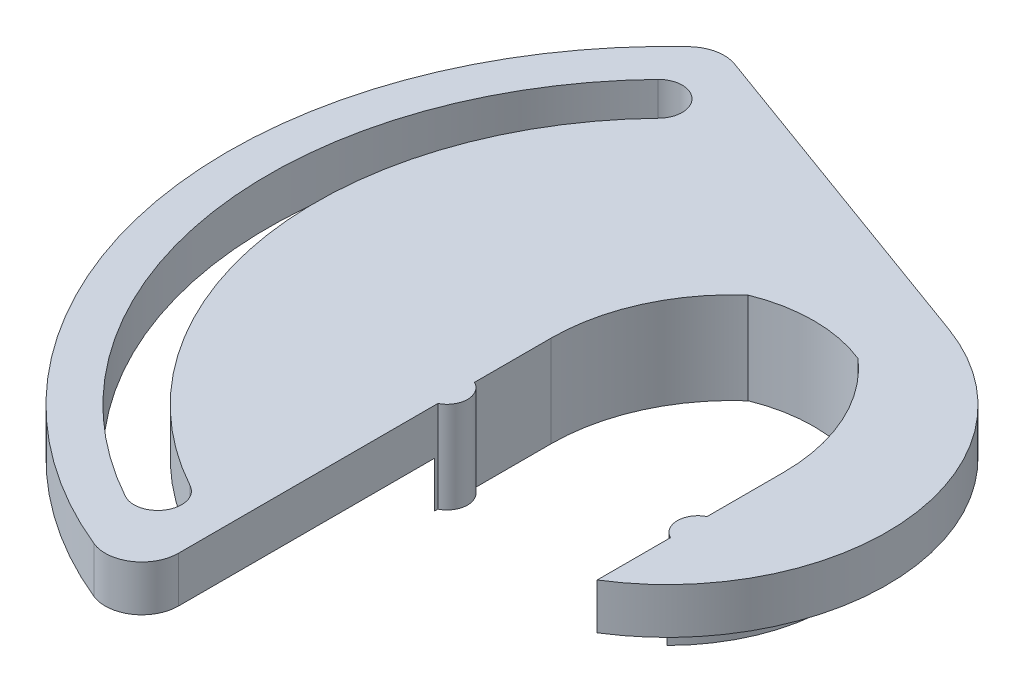
SolidWorks part; units mm, degrees
material "ABS"
ref_plane "Front Plane" through (0, 0, 0) normal (0, 0, 1) x (1, 0, 0)
ref_plane "Top Plane" through (0, 0, 0) normal (0, 1, 0) x (1, 0, 0)
ref_plane "Right Plane" through (0, 0, 0) normal (1, 0, 0) x (0, 0, -1)
sketch "Sketch1" plane through (0, 0, 0) normal (0, 1, 0) x (1, 0, 0)
  line L0 (0, -8) -> (0, 8) construction
  line L1 (-6.35, 0) -> (6.35, 0) construction
  line L2 (-6.35, 0) -> (-6.35, -6.3779)
  line L3 (6.35, -6.3779) -> (6.35, 0)
  arc A0 (-3, 7.4162) -> (3, 7.4162) centre (0, 0) cw
  arc A1 (-3, -7.4162) -> (3, -7.4162) centre (0, 0) ccw construction
  arc A2 (-3, 7.4162) -> (-3, -7.4162) centre (3.534, 0) ccw construction
  arc A3 (-3, 7.4162) -> (-6.35, 0) centre (3.534, 0) ccw
  arc A4 (3, 7.4162) -> (6.35, 0) centre (-3.534, 0) cw
  arc A5 (-6.35, -6.3779) -> (6.35, -6.3779) centre (0, 0) cw
  dimension "D4" = 1
  dimension "D1" = 12.7
  dimension "D2" = 8
  dimension "D3" = 3
extrude "Boss-Extrude1" add sketch "Sketch1" along normal blind 2.5
sketch "Sketch2" plane through (0, 2.5, 0) normal (0, 1, 0) x (1, 0, 0)
  line L0 (4.1042, 11.2763) -> (-15.4269, 18.3851)
  line L4 (-6.35, -23.1447) -> (-6.35, -6.3779)
  line L5 (0, 0) -> (-15.4269, 18.3851) construction
  line L7 (0, 0) -> (0, -7.7251) construction
  line L10 (-6.35, -6.3779) -> (-6.35, 0)
  line L11 (6.35, 0) -> (6.35, -6.3779)
  line L12 (-6.35, -6.3779) -> (-6.35, 0)
  line L13 (6.35, 0) -> (6.35, -10.1822)
  arc A0 (6.35, -10.1822) -> (4.1042, 11.2763) centre (0, 0) ccw
  arc A6 (-6.35, -23.1447) -> (-15.4269, 18.3851) centre (0, 0) cw
  arc A12 (6.35, -6.3779) -> (-6.35, -6.3779) centre (0, 0) ccw
  arc A13 (6.35, 0) -> (3, 7.4162) centre (-3.534, 0) ccw
  arc A14 (3, 7.4162) -> (-3, 7.4162) centre (0, 0) ccw
  arc A15 (-3, 7.4162) -> (-6.35, 0) centre (3.534, 0) ccw
  arc A17 (6.35, 0) -> (3, 7.4162) centre (-3.534, 0) ccw
  arc A18 (3, 7.4162) -> (-3, 7.4162) centre (0, 0) ccw
  arc A19 (-3, 7.4162) -> (-6.35, 0) centre (3.534, 0) ccw
  dimension "D1" = 24
  dimension "D4" = 12
  dimension "D2" = 140
  dimension "D3" = 0
extrude "Boss-Extrude2" add sketch "Sketch2" along normal blind 2.5 separate body
fillet "Fillet1" radius 2 2 edges at (-6.35, 3.75, 23.1447) (-15.4269, 3.75, -18.3851)
ref_axis "Axis1" through (0, -0.25, 0) along (0, 1, 0)
sketch "Sketch3" plane through (0, 5, 0) normal (0, 1, 0) x (1, 0, 0)
  line L0 (-18.9833, -2.8767) -> (-20.2686, -3.0715) construction
  line L1 (-21.5539, -3.2662) -> (-20.2686, -3.0715) construction
  line L2 (-14.74, 14.2472) -> (-11.9601, 17.1233) construction
  line L3 (-9.8572, -17.9746) -> (0, 0) construction
  line L4 (0, 0) -> (-14.74, 14.2472) construction
  line L5 (-9.8572, -17.9746) -> (-6.35, -19.8979) construction
  line L7 (-6.35, -20.3538) -> (-6.35, 0) construction
  line L8 (4.1042, 11.2763) -> (-14.3099, 17.9785) construction
  arc A0 (-9.8572, -17.9746) -> (-14.74, 14.2472) centre (0, 0) cw construction
  arc A1 (-9.2321, -16.8347) -> (-10.4823, -19.1144) centre (-9.8572, -17.9746) cw
  arc A2 (-15.6748, 15.1506) -> (-13.8053, 13.3437) centre (-14.74, 14.2472) cw
  arc A3 (-15.6748, 15.1506) -> (-10.4823, -19.1144) centre (0, 0) ccw
  arc A4 (-13.8053, 13.3437) -> (-9.2321, -16.8347) centre (0, 0) ccw
  dimension "D1" = 1.3
  dimension "D2" = 4
  dimension "D4" = 20.5
  dimension "D3" = 1.3
extrude "Cut-Extrude1" cut sketch "Sketch3" against normal through all
sketch "Sketch4" plane through (0, 2.5, 0) normal (0, -1, 0) x (1, 0, 0)
  arc A0 (-9.8572, 17.9746) -> (-14.74, -14.2472) centre (0, 0) ccw construction
  arc A1 (-9.8572, 17.9746) -> (-14.74, -14.2472) centre (0, 0) ccw
sketch "Sketch6" plane through (0, 5, 0) normal (0, 1, 0) x (1, 0, 0)
  line L0 (6.35, -6.1822) -> (6.35, -4.1822)
  line L1 (6.35, 0) -> (6.35, -10.1822) construction
  arc A0 (6.35, -6.1822) -> (6.35, -4.1822) centre (6.85, -5.1822) cw
  dimension "D1" = 0.5
  dimension "D2" = 2
  dimension "D3" = 4
extrude "Boss-Extrude3" add sketch "Sketch6" against normal up to surface (5 mm away) up to face at (0, 0, -3.1266)
mirror "Mirror1" about plane through (0, 0, 0) normal (1, 0, 0) of "Boss-Extrude3"
